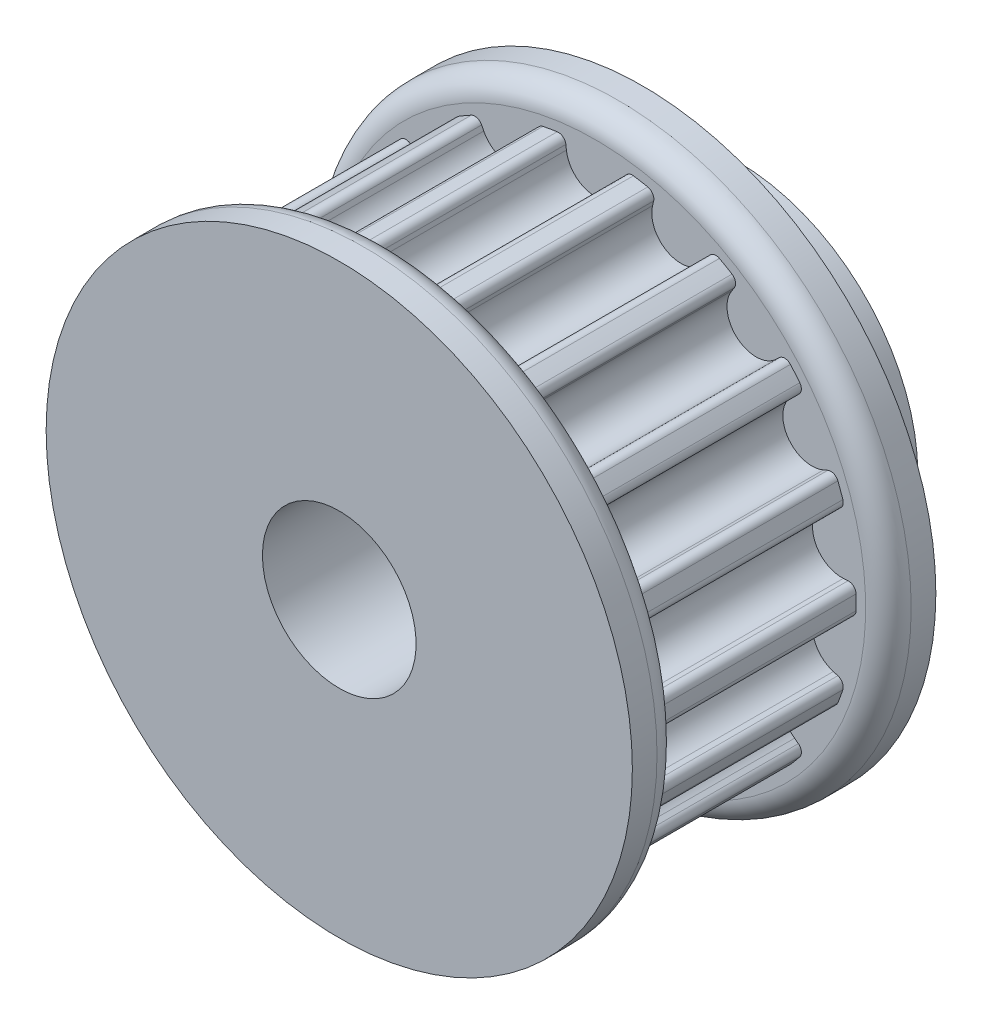
SolidWorks part; units mm, degrees
material "6061 합금"
ref_plane "정면" through (0, 0, 0) normal (0, 0, 1) x (1, 0, 0)
ref_plane "윗면" through (0, 0, 0) normal (0, 1, 0) x (1, 0, 0)
ref_plane "우측면" through (0, 0, 0) normal (1, 0, 0) x (0, 0, -1)
sketch "스케치3" plane through (0, 0, 0) normal (0, 0, 1) x (1, 0, 0)
  line L0 (0, 0) -> (0, 13.7524) construction
  line L1 (0, 0) -> (-4.8991, 13.4601) construction
  line L2 (0, 13.7524) -> (0, 15.4524) construction
  line L3 (-1.5246, 13.0088) -> (-1.6008, 13.659)
  line L4 (1.5246, 13.0088) -> (1.6008, 13.659)
  circle A0 centre (0, 0) radius 14.3239 construction
  circle A1 centre (0, 0) radius 15.4524 construction
  circle A2 centre (0, 0) radius 13.7524
  circle A3 centre (0, 13.1874) radius 1.535
  dimension "D2" = 28.6479
  dimension "D5" = 3.07
  dimension "D3" = 27.5049
  dimension "D1" = 20
  dimension "D4" = 2.1
  dimension "D6" = 3.8
extrude "보스-돌출2" add sketch "스케치3" along normal mid plane 11 contours A2
extrude "컷-돌출2" cut sketch "스케치3<3>" against normal through all both and the other way through all contours A3 A2 L3 | A2 A3 | A3 L4 A2 region at (0, 12.8159, 0) region at (-1.5387, 13.5029, 0) region at (1.5387, 13.5029, 0)
sketch "스케치3<3>" plane through (0, 0, 0) normal (0, 0, 1) x (1, 0, 0) same geometry as "스케치3"
fillet "필렛1" radius 0.4 2 edges at (1.6008, 13.659, 0) (-1.6008, 13.659, 0)
pattern_circular "원형 패턴1" count 18 over 360 about axis through (0, 0, 5.5) along (0, 0, -1) of "컷-돌출2", "필렛1"
sketch "스케치12" plane through (0, 0, 5.5) normal (0, 0, 1) x (1, 0, 0)
  circle A0 centre (0, 0) radius 15.4524 construction
  circle A1 centre (0, 0) radius 15.4524
extrude "보스-돌출4" add sketch "스케치12" along normal blind 2.5
sketch "스케치13" plane through (0, 0, -5.5) normal (0, 0, -1) x (-1, 0, 0)
  circle A0 centre (0, 0) radius 15.4524 construction
  circle A1 centre (0, 0) radius 15.4524
extrude "보스-돌출5" add sketch "스케치13" along normal blind 2.5
fillet "필렛2" radius 1.2 2 edges at (15.4524, 0, 5.5) (-15.4524, 0, -5.5)
sketch "스케치5" plane through (0, 0, -8) normal (0, 0, -1) x (-1, 0, 0)
  circle A2 centre (0, 0) radius 9.5
  dimension "D1" = 19
extrude "보스-돌출3" add sketch "스케치5" along normal blind 5
sketch "스케치4" plane through (0, 0, 8) normal (0, 0, -1) x (-1, 0, 0)
  circle A0 centre (0, 0) radius 4.05
  dimension "D1" = 8.1
extrude "컷-돌출3" cut sketch "스케치4" along normal through all
hole_wizard "M4x0.7 탭을 위한 탭 드릴1" positions "스케치7" profile "스케치8" hole size "M4x0.7" standard "Ansi Metric" end condition through all
sketch "스케치7" plane through (0, 0, 0) normal (0, 1, 0) x (1, 0, 0)
  line L0 (0, 13) -> (0, 8) construction
  line L1 (9.5, 13) -> (-9.5, 13) construction
  line L4 (9.5, 8) -> (-9.5, 8) construction
  point P0 (0, 10.5)
sketch "스케치8" plane through (0, 0, -10.5) normal (1, 0, 0) x (0, 0, -1)
  line L0 (0, 0) -> (0, 15.4524)
  line L1 (0, 15.4524) -> (1.5, 15.4524)
  line L2 (1.5, 15.4524) -> (1.5, 0)
  line L5 (1.5, 0) -> (0, 0)
  line L11 (0, -6.35) -> (0, 107.95) construction
  dimension "관통 구멍 지름" = 3
  dimension "관통 구멍 깊이" = 15.4524
sketch "스케치14" plane through (0, 0, 8) normal (0, 0, 1) x (1, 0, 0)
  circle A0 centre (0, 0) radius 16
  circle A1 centre (0, 0) radius 18.5
  dimension "D1" = 2.5
  dimension "D2" = 32
extrude "보스-돌출6" [suppressed] add sketch "스케치14" against normal up to surface (13 mm away) separate body up to face at (-9.5, 0, -8)
equation "\"n\"= 18'number of teeth"
equation "\"D2@스케치3\"=5*\"n\"/(PI)"
equation "\"D1@스케치3\"=360/\"n\""
equation "\"D1@원형 패턴1\"=\"n\""
equation "\"D3@스케치3\"=\"D2@스케치3\"-2*0.225*2.54"
